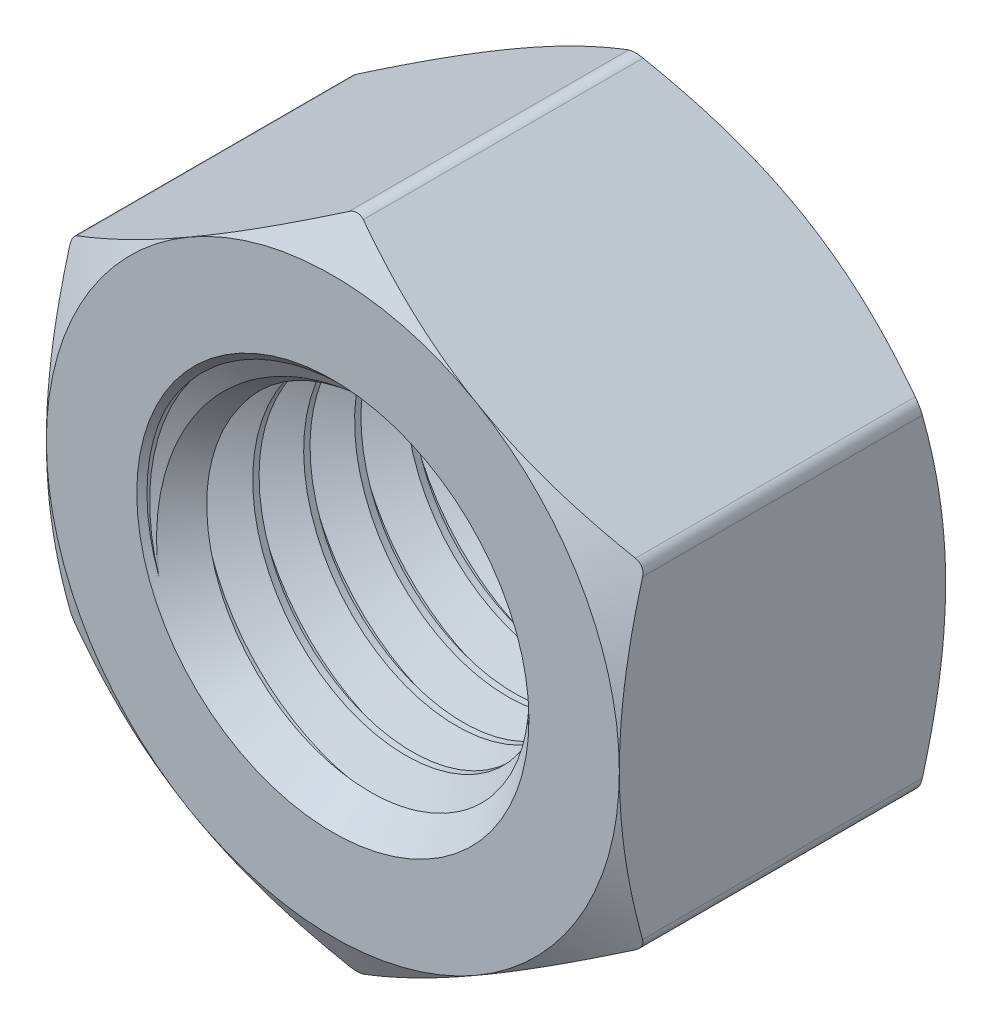
SolidWorks part; units mm, degrees
ref_plane "Front" through (0, 0, 0) normal (0, 0, 1) x (1, 0, 0)
ref_plane "Top" through (0, 0, 0) normal (0, 1, 0) x (1, 0, 0)
ref_plane "Right" through (0, 0, 0) normal (1, 0, 0) x (0, 0, -1)
sketch "Sketch1" plane through (0, 0, 0) normal (0, 0, 1) x (1, 0, 0)
  line L0 (0, 9.525) -> (0, 6.985) construction
  line L1 (-14.2875, 8.2489) -> (-14.2875, -8.2489)
  line L2 (-14.2875, -8.2489) -> (0, -16.4978)
  line L3 (0, -16.4978) -> (14.2875, -8.2489)
  line L4 (14.2875, -8.2489) -> (14.2875, 8.2489)
  line L5 (14.2875, 8.2489) -> (0, 16.4978)
  line L6 (0, 16.4978) -> (-14.2875, 8.2489)
  circle A0 centre (0, 0) radius 14.2875 construction
  circle A1 centre (0, 0) radius 9.525 construction
  point P10 (0, 9.525)
  dimension "Width" = 28.575
  dimension "Thread Size" = 19.05
  dimension "Thread Pitch" = 2.54
sketch "Sketch2" plane through (0, 0, 0) normal (1, 0, 0) x (0, 0, -1)
  line L0 (-8.1359, 0) -> (8.1359, 0) construction
  line L1 (-8.1359, 16.4978) -> (8.1359, 16.4978) construction
  dimension "Height" = 16.2719
sketch "Sketch15" plane through (0, 0, 0) normal (0, 0, 1) x (1, 0, 0)
  line L1 (0, 16.4978) -> (-14.2875, 8.2489)
  line L2 (-14.2875, 8.2489) -> (-14.2875, -8.2489)
  line L3 (-14.2875, -8.2489) -> (0, -16.4978)
  line L4 (0, -16.4978) -> (14.2875, -8.2489)
  line L5 (14.2875, -8.2489) -> (14.2875, 8.2489)
  line L6 (14.2875, 8.2489) -> (0, 16.4978)
  circle A0 centre (0, 0) radius 14.2875 construction
extrude "Boss-Extrude2" add sketch "Sketch15" along normal mid plane 16.2719
sketch "Sketch16" plane through (0, 0, 0) normal (0, 0, 1) x (1, 0, 0)
  circle A0 centre (0, 0) radius 9.525 construction
  circle A1 centre (0, 0) radius 9.525
sketch "Sketch4" plane through (0, 0, -8.1359) normal (0, 0, -1) x (-1, 0, 0)
  circle A0 centre (0, 0) radius 9.525 construction
  circle A1 centre (0, 0) radius 9.525
extrude "Cut-Extrude4" cut sketch "Sketch16" against normal through all both and the other way through all
sketch "Sketch7" plane through (0, 0, 8.1359) normal (0, 0, 1) x (1, 0, 0)
  circle A0 centre (0, 0) radius 14.2875 construction
  circle A1 centre (0, 0) radius 14.2875
extrude "Cut-Extrude5" cut sketch "Sketch7" against normal through all draft 60 flip side to cut
mirror "Mirror4" about plane through (0, 0, 0) normal (0, 0, 1) of "Cut-Extrude5"
fillet "Fillet2" radius 0.7144 6 edges at (-14.2875, 8.2489, 0) (-14.2875, -8.2489, 0) (0, -16.4978, 0) (14.2875, -8.2489, 0) (14.2875, 8.2489, 0) (0, 16.4978, 0)
sketch "Sketch8" plane through (0, 0, 8.1359) normal (0, 0, 1) x (1, 0, 0)
  line L0 (2.4653, -9.2004) -> (0, 0) construction
  line L2 (0, 9.525) -> (0, 6.985) construction
  circle A0 centre (0, 0) radius 9.525 construction
  point P0 (2.4653, -9.2004)
  dimension "D1" = 15
sketch "Sketch13" plane through (0, 0, -8.1359) normal (0, 0, -1) x (-1, 0, 0)
  circle A0 centre (0, 0) radius 9.525 construction
  circle A1 centre (0, 0) radius 9.525
extrude "Boss-Extrude1" add sketch "Sketch13" against normal up to surface (16.2719 mm away) separate body up to face at (9.525, 0, 8.1359)
curve "Helix/Spiral3" pitch 2.54 height 18.8119 radius 9.525 centre (0, 0, -8.1359) axis (0, 0, 1) start towards (0, 1, 0)
sketch "Sketch12" plane through (0, 0, 0) normal (1, 0, 0) x (0, 0, -1)
  line L0 (10.3584, 9.525) -> (8.1359, 9.525)
  line L1 (10.3584, 9.525) -> (9.4059, 7.8752)
  line L2 (9.4059, 7.8752) -> (9.0884, 7.8752)
  line L3 (9.0884, 7.8752) -> (8.1359, 9.525)
  line L4 (9.2472, 7.8752) -> (9.2472, 9.525) construction
  line L5 (8.6122, 8.7001) -> (9.8822, 8.7001) construction
  dimension "D1" = 60
  dimension "D2" = 0.3175
  dimension "D3" = 1.27
sweep "Cut-Sweep1" cut profiles "Sketch12" path "Helix/Spiral3" align with end faces yes
sketch "Sketch17" plane through (0, 0, 8.1359) normal (0, 0, 1) x (1, 0, 0)
  circle A1 centre (0, 0) radius 9.525
  circle A2 centre (0, 0) radius 9.525
  dimension "D1" = 0
extrude "Boss-Extrude3" add sketch "Sketch17" against normal up to surface (16.2719 mm away) up to face at (9.525, 0, -8.1359)
combine bodies "Combine1" operation type subtract main body 127 bodies to subtract 118
sketch "Sketch10" plane through (0, 0, 8.1359) normal (0, 0, 1) x (1, 0, 0)
  circle A0 centre (0, 0) radius 9.525 construction
  circle A1 centre (0, 0) radius 9.525 construction
  circle A2 centre (0, 0) radius 9.779
  dimension "D1" = 0.254
extrude "Cut-Extrude2" cut sketch "Sketch10" against normal through all draft 45
sketch "Sketch11" plane through (0, 0, -8.1359) normal (0, 0, -1) x (-1, 0, 0)
  circle A1 centre (0, 0) radius 9.779 construction
  circle A2 centre (0, 0) radius 9.779
extrude "Cut-Extrude3" cut sketch "Sketch11" against normal through all draft 45
equation "\"D1\"= \"Height@Sketch2\""
equation "\"D3@Helix/Spiral3\"=\"Height@Sketch2\"+\"Thread Pitch@Sketch1\""
equation "\"D4@Helix/Spiral3\"=\"Thread Pitch@Sketch1\""
equation "\"D2@Sketch12\" = \"D4@Helix/Spiral3\"*.125"
equation "\"D3@Sketch12\" = \"D4@Helix/Spiral3\"*.50"
equation "\"D1@Boss-Extrude2\"=\"Height@Sketch2\""
equation "\"D1@Fillet2\"=\"Width@Sketch1\"*0.025"
equation "\"D1@Sketch10\"=\"Thread Pitch@Sketch1\"*0.1"
